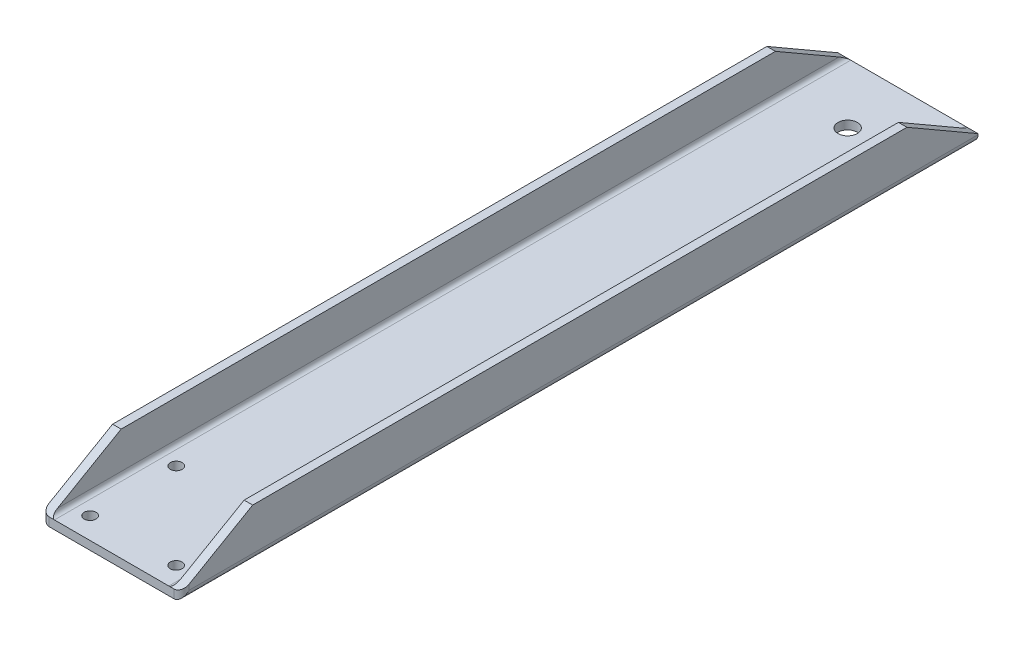
SolidWorks part; units mm, degrees
material "Fiberglass, GP03"
ref_plane "Front Plane" through (0, 0, 0) normal (0, 0, 1) x (1, 0, 0)
ref_plane "Top Plane" through (0, 0, 0) normal (0, 1, 0) x (1, 0, 0)
ref_plane "Right Plane" through (0, 0, 0) normal (1, 0, 0) x (0, 0, -1)
ref_axis "Axis1" through (0, 0, -88.99) along (0, 0, 1)
ref_axis "Axis2" through (0, -55, 0) along (0, 1, 0)
ref_axis "Axis3" through (-88.99, 0, 0) along (1, 0, 0)
sketch "Sketch1" plane through (0, 0, 0) normal (0, 0, 1) x (1, 0, 0)
  line L0 (-32.5437, 23.0187) -> (-32.5437, 0)
  line L1 (-32.5437, 0) -> (32.5437, 0)
  line L2 (32.5437, 0) -> (32.5437, 23.0187)
  line L3 (32.5437, 23.0187) -> (28.575, 23.0187)
  line L4 (28.575, 23.0187) -> (28.575, 3.9687)
  line L5 (28.575, 3.9687) -> (-28.575, 3.9687)
  line L6 (0, 0) -> (0, 3.9687) construction
  line L7 (-32.5437, 0) -> (-32.5437, 23.0187)
  line L8 (-32.5437, 23.0187) -> (-28.575, 23.0187)
  line L9 (-28.575, 23.0187) -> (-28.575, 3.9687)
  dimension "D1" = 3.9688
  dimension "D2" = 19.05
  dimension "D3" = 65.0875
extrude "Boss-Extrude1" add sketch "Sketch1" along normal blind 370 contours L6 L1 L2 L3 L4 L5 | L1 L6 L5 L9 L8 L0 region at (-30.5594, 22.6201, 0) region at (0.3986, 1.9844, 0)
sketch "Sketch2" plane through (-32.5437, 0, 0) normal (-1, 0, 0) x (0, 0, 1)
  line L0 (0, 3.9687) -> (32.9956, 23.0187)
  line L1 (370, 23.0187) -> (0, 23.0187) construction
  line L2 (32.9956, 23.0187) -> (0, 23.0187)
  line L3 (0, 23.0187) -> (0, 3.9687)
  line L4 (185, 23.0188) -> (185, 0) construction
  line L5 (370, 0) -> (0, 0) construction
  line L6 (370, 23.0187) -> (370, 3.9688)
  line L7 (337.0044, 23.0188) -> (370, 23.0187)
  line L8 (370, 3.9688) -> (337.0044, 23.0188)
  dimension "D1" = 30
extrude "Cut-Extrude1" cut sketch "Sketch2" against normal through all
hole_wizard "M5 Clearance Hole1" positions "Sketch5" profile "Sketch4" hole size "M5" standard "ANSI Metric" end condition through all
sketch "Sketch5" plane through (0, 3.9687, 0) normal (0, 1, 0) x (1, 0, 0)
  line L0 (0, -370) -> (0, -340) construction
  line L1 (28.575, -370) -> (-28.575, -370) construction
  line L2 (0, -340) -> (23.3005, -340) construction
  point P0 (20, -360)
  point P10 (20, -320)
  point P11 (-20, -320)
  point P12 (-20, -360)
  dimension "D1" = 40
  dimension "D2" = 40
  dimension "D3" = 10
sketch "Sketch4" plane through (20, 3.9687, 360) normal (1, 0, 0) x (0, 0, 1)
  line L0 (0, 0) -> (0, 3.9687)
  line L1 (0, 3.9687) -> (2.75, 3.9687)
  line L2 (2.75, 3.9687) -> (2.75, 0)
  line L5 (2.75, 0) -> (0, 0)
  line L11 (0, -6.35) -> (0, 107.95) construction
  dimension "Thru Hole Dia." = 5.5
  dimension "Thru Hole Depth" = 3.9687
hole_wizard "M8 Clearance Hole1" positions "Sketch7" profile "Sketch6" hole size "M8" standard "ANSI Metric" end condition through all
sketch "Sketch7" plane through (0, 3.9687, 0) normal (0, 1, 0) x (1, 0, 0)
  line L0 (0, 0) -> (0, -28) construction
  circle A0 centre (0, -28) radius 10
  point P0 (0, -28)
  dimension "D2" = 20
  dimension "D1" = 28
sketch "Sketch6" plane through (0, 3.9687, 28) normal (1, 0, 0) x (0, 0, 1)
  line L0 (0, 0) -> (0, 3.9687)
  line L1 (0, 3.9687) -> (4.5, 3.9687)
  line L2 (4.5, 3.9687) -> (4.5, 0)
  line L5 (4.5, 0) -> (0, 0)
  line L11 (0, -6.35) -> (0, 107.95) construction
  dimension "Thru Hole Dia." = 9
  dimension "Thru Hole Depth" = 3.9687
fillet "Fillet1" radius 2 2 edges at (28.575, 3.9687, 185) (-28.575, 3.9688, 185)
fillet "Fillet2" radius 3.5 2 edges at (32.5437, 0, 185) (-32.5437, 0, 185)
sketch "Sketch8" plane through (0, 0, 0) normal (0, -1, 0) x (1, 0, 0)
  line L0 (-32.5437, 0) -> (-32.5437, 370) construction
  line L1 (-29.0437, 370) -> (-32.5437, 370) construction
  line L3 (-32.5438, 366.5) -> (-32.5437, 370)
  line L4 (-29.0437, 370) -> (-32.5437, 370)
  line L5 (29.0437, 370) -> (32.5437, 370)
  line L6 (0, 370) -> (0, 326.7934) construction
  line L7 (32.5438, 366.5) -> (32.5437, 370)
  line L8 (-29.0437, 370) -> (29.0437, 370) construction
  arc A0 (-29.0437, 370) -> (-32.5438, 366.5) centre (-29.0437, 366.5) ccw
  arc A1 (29.0437, 370) -> (32.5438, 366.5) centre (29.0437, 366.5) cw
  dimension "D1" = 3.5
extrude "Cut-Extrude2" cut sketch "Sketch8" against normal through all
